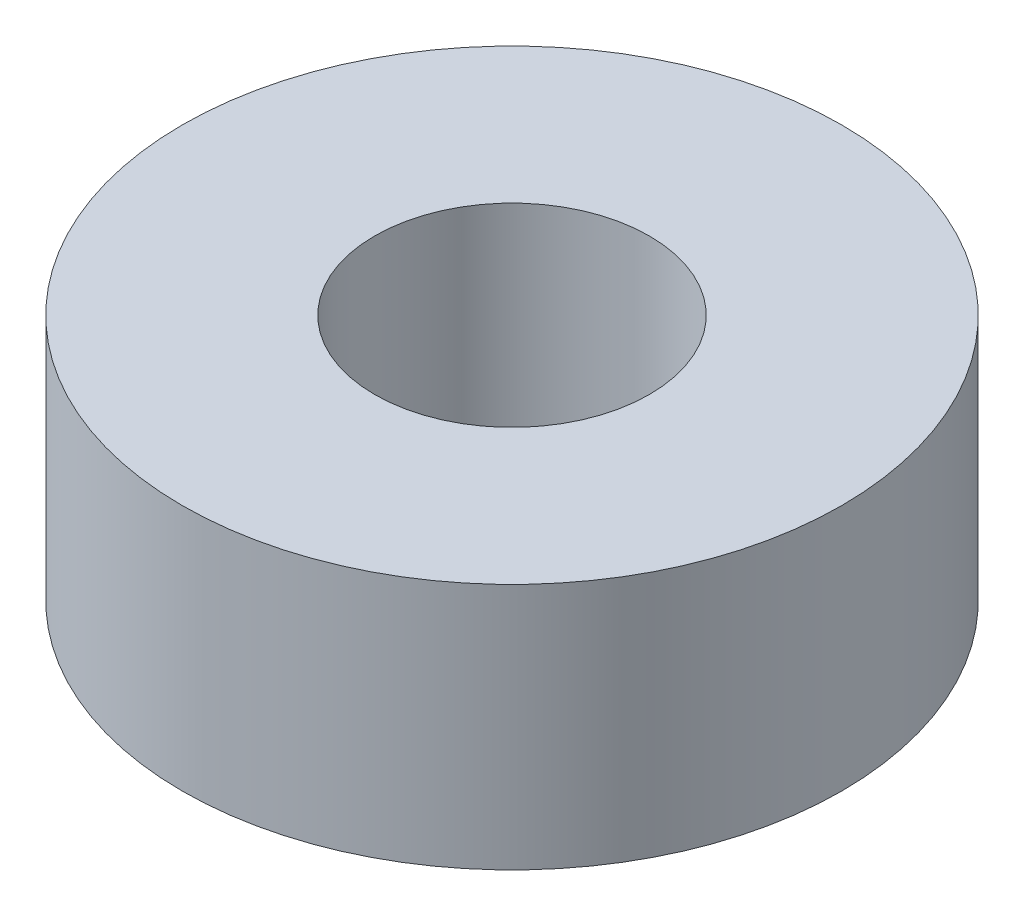
SolidWorks part; units mm, degrees
ref_plane "Front Plane" through (0, 0, 0) normal (0, 0, 1) x (1, 0, 0)
ref_plane "Top Plane" through (0, 0, 0) normal (0, 1, 0) x (1, 0, 0)
ref_plane "Right Plane" through (0, 0, 0) normal (1, 0, 0) x (0, 0, -1)
sketch "Sketch1" plane through (0, 0, 0) normal (0, 1, 0) x (1, 0, 0)
  circle A0 centre (0, 0) radius 12
  circle A1 centre (0, 0) radius 5
  dimension "D1" = 24
  dimension "D2" = 10
extrude "Boss-Extrude1" add sketch "Sketch1" along normal blind 4.5 and the other way blind 4.5
